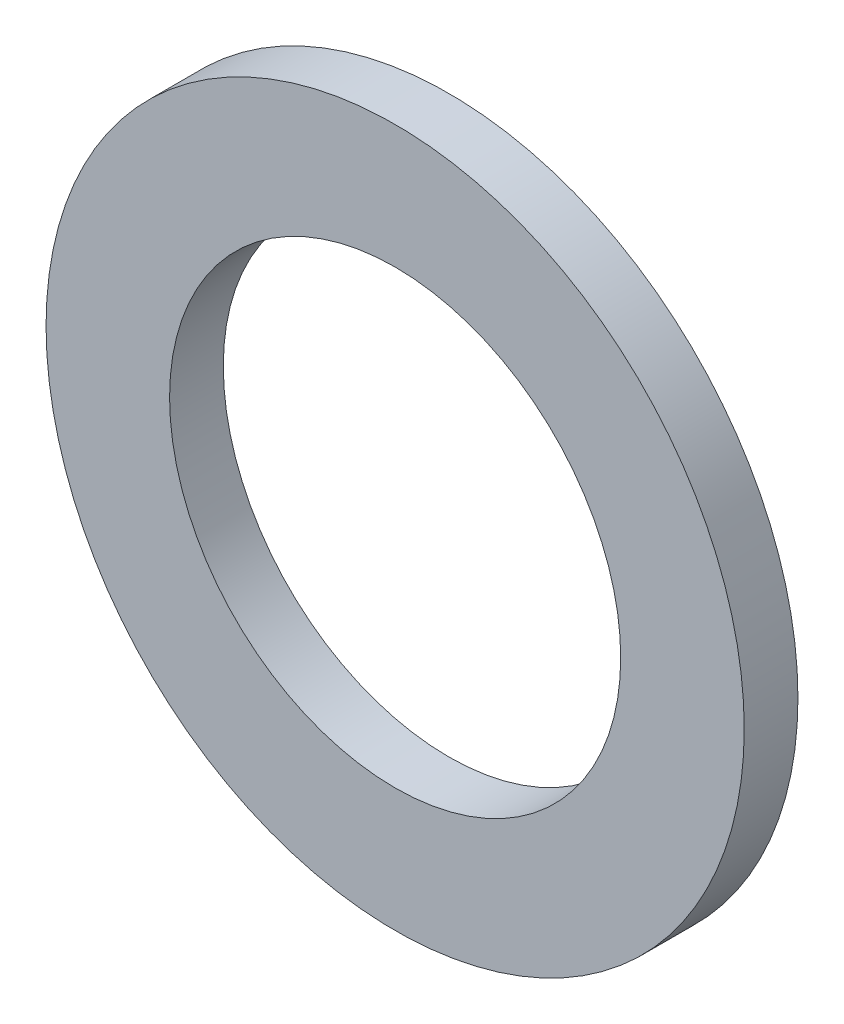
SolidWorks part; units mm, degrees
ref_plane "Front Plane" through (0, 0, 0) normal (0, 0, 1) x (1, 0, 0)
ref_plane "Top Plane" through (0, 0, 0) normal (0, 1, 0) x (1, 0, 0)
ref_plane "Right Plane" through (0, 0, 0) normal (1, 0, 0) x (0, 0, -1)
sketch "Sketch1" plane through (0, 0, 0) normal (0, 0, 1) x (1, 0, 0)
  circle A0 centre (0, 0) radius 4.2
  circle A1 centre (0, 0) radius 6.5
  dimension "D1" = 8.4
  dimension "D2" = 13
extrude "Boss-Extrude1" add sketch "Sketch1" along normal blind 1
